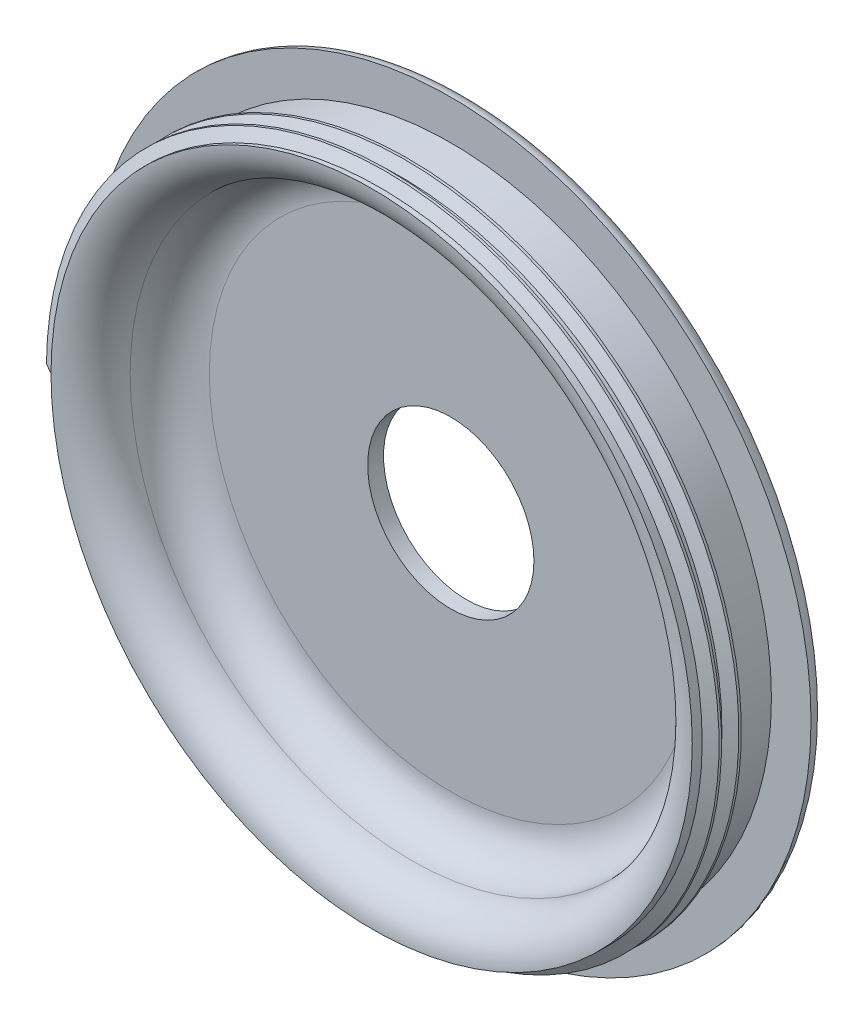
SolidWorks part; units mm, degrees
ref_plane "Plan de face" through (0, 0, 0) normal (0, 0, 1) x (1, 0, 0)
ref_plane "Plan de dessus" through (0, 0, 0) normal (0, 1, 0) x (1, 0, 0)
ref_plane "Plan de droite" through (0, 0, 0) normal (1, 0, 0) x (0, 0, -1)
sketch "Esquisse1" plane through (0, 0, 0) normal (0, 0, 1) x (1, 0, 0)
  circle A0 centre (0, 0) radius 45.5
  circle A1 centre (0, 0) radius 10.5
  dimension "D1" = 91
  dimension "D2" = 21
extrude "Boss.-Extru.1" add sketch "Esquisse1" along normal blind 2
sketch "Esquisse2" plane through (0, 0, 2) normal (0, 0, 1) x (1, 0, 0)
  circle A0 centre (0, 0) radius 40.5
  circle A1 centre (0, 0) radius 35.5
  circle A2 centre (0, 0) radius 45.5 construction
  dimension "D1" = 5
  dimension "D2" = 5
extrude "Boss.-Extru.2" add sketch "Esquisse2" along normal blind 10
thread "Filetage2" pitch 2.5 method extrude profile "Profil de filetage2" start angle 0, offset 0, length 5, pitch 2.5, diameter 81
ref_plane "Plan2" through (-40.5, 0, 12) normal (0, -1, 0) x (-1, 0, 0)
sketch "Profil de filetage2" plane through (-40.5, 0, 12) normal (0, -1, 0) x (-1, 0, 0)
  line L0 (0, 0) -> (0, 2.5) construction
  line L1 (0, 0) -> (1.3532, 0.7812)
  line L2 (1.3532, 0.7812) -> (1.3532, 1.0937)
  line L3 (1.3532, 1.0937) -> (0, 1.875)
  line L4 (1.3532, 0.9375) -> (0, 0.9375) construction
  line L11 (0, 0) -> (0, 1.875)
  point P2 (0, 0)
  dimension "Pitch" = 2.5
  dimension "Profile_Angle" = 60
  dimension "Profile_Land" = 0.3125
  dimension "Profile_Height" = 1.3532
fillet "Congé1" radius 5 2 edges at (35.5, 0, 2) (35.5, 0, 12)
fillet "Congé2" radius 2 1 edges at (45.5, 0, 0)
